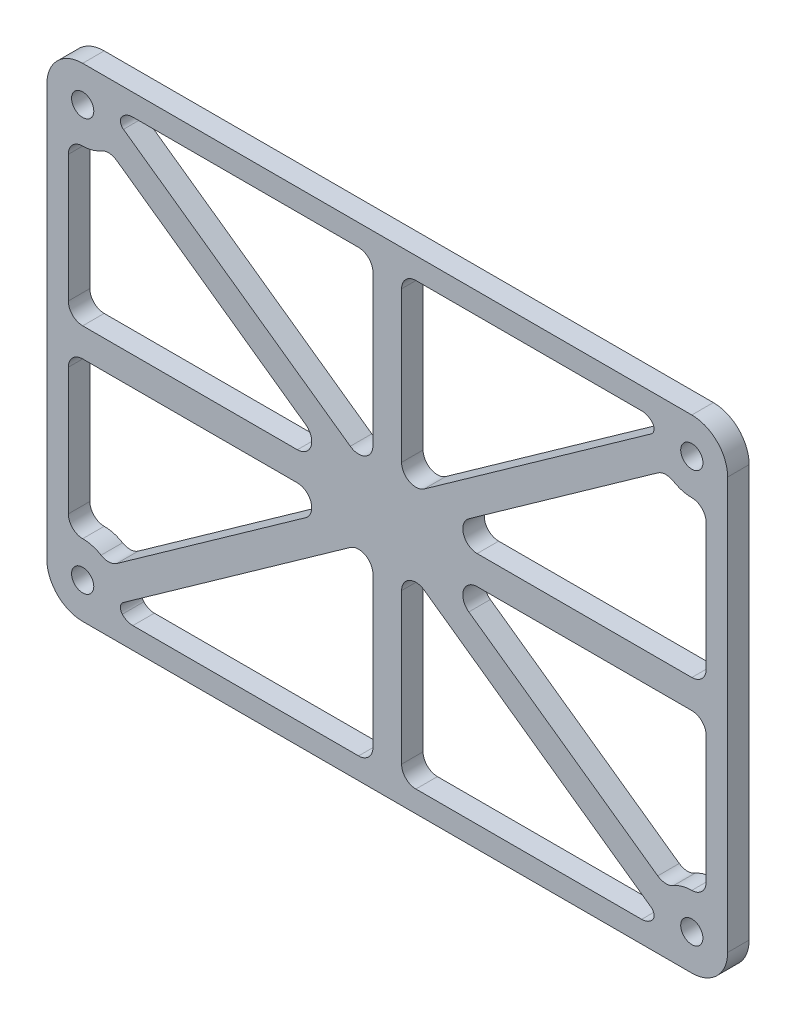
SolidWorks part; units mm, degrees
material "Thornel Mat VMA"
ref_plane "前视基准面" through (0, 0, 0) normal (0, 0, 1) x (1, 0, 0)
ref_plane "上视基准面" through (0, 0, 0) normal (0, 1, 0) x (1, 0, 0)
ref_plane "右视基准面" through (0, 0, 0) normal (1, 0, 0) x (0, 0, -1)
sketch "草图1" plane through (0, 0, 0) normal (0, 0, 1) x (1, 0, 0)
  line L0 (0, 0) -> (-50000, 0) construction
  line L1 (47.5, -33.725) -> (-47.5, -33.725)
  line L2 (47.5, -33.725) -> (47.5, 33.725)
  line L3 (47.5, 33.725) -> (-47.5, 33.725)
  line L4 (-47.5, -33.725) -> (-47.5, 33.725)
  line L5 (47.5, -33.725) -> (-47.5, 33.725) construction
  line L6 (47.5, 33.725) -> (-47.5, -33.725) construction
  line L7 (0, 0) -> (0, 50000) construction
  line L8 (-44.5, -2) -> (-44.5, -24.1424)
  line L9 (-6.2716, -2) -> (-38.9514, -25.2026)
  line L10 (-44.5, -2) -> (-6.2716, -2)
  line L11 (-6.2716, 2) -> (-38.9514, 25.2026)
  line L12 (-44.5, 2) -> (-6.2716, 2)
  line L13 (-44.5, 2) -> (-44.5, 24.1424)
  line L14 (-2, 30.725) -> (-37.9174, 30.725)
  line L15 (-2, 3.8728) -> (-37.5131, 29.0872)
  line L16 (-2, 3.8728) -> (-2, 30.725)
  line L17 (-2, -3.8728) -> (-2, -30.725)
  line L18 (-2, -30.725) -> (-37.9174, -30.725)
  line L19 (-2, -3.8728) -> (-37.5131, -29.0872)
  line L20 (2, -30.725) -> (37.9174, -30.725)
  line L21 (2, -3.8728) -> (2, -30.725)
  line L22 (2, -3.8728) -> (37.5131, -29.0872)
  line L23 (6.2716, -2) -> (38.9514, -25.2026)
  line L24 (44.5, -2) -> (6.2716, -2)
  line L25 (44.5, -2) -> (44.5, -24.1424)
  line L26 (44.5, 2) -> (6.2716, 2)
  line L27 (6.2716, 2) -> (38.9514, 25.2026)
  line L28 (44.5, 2) -> (44.5, 24.1424)
  line L29 (2, 3.8728) -> (2, 30.725)
  line L30 (2, 3.8728) -> (37.5131, 29.0872)
  line L31 (2, 30.725) -> (37.9174, 30.725)
  circle A0 centre (-42.5, 28.725) radius 1.55
  circle A2 centre (42.5, 28.725) radius 1.55
  circle A3 centre (42.5, -28.725) radius 1.55
  circle A4 centre (-42.5, -28.725) radius 1.55
  circle A5 centre (-42.5, 28.725) radius 5
  circle A6 centre (-42.5, -28.725) radius 5
  circle A7 centre (42.5, -28.725) radius 5
  circle A8 centre (42.5, 28.725) radius 5
  point P0 (0, 0)
  dimension "D1" = 3.1
  dimension "D5" = 5
  dimension "D6" = 10
  dimension "D2" = 85
  dimension "D3" = 57.45
  dimension "D4" = 5
  dimension "D7" = 2
  dimension "D8" = 3
  dimension "D9" = 4
  dimension "D10" = 3
  dimension "D11" = 2
extrude "凸台-拉伸1" add sketch "草图1" along normal blind 3 contours A8 L3 A5 L14 L16 L15 L11 L12 L13 L4 A6 L8 L10 L9 L19 L17 L18 L1 A7 L20 L21 L22 L23 L24 L25 L2 L28 L26 L27 L30 L29 L31 | A5 A0 | A8 A2 | A7 A3 | A6 A4 region at (0, 0, 0) region at (39.8388, -32.79, 0) region at (-45.9355, -32.1605, 0) region at (46.565, 26.0638, 0) region at (-45.9355, 32.1605, 0)
fillet "圆角1" radius 2 32 edges at (38.9514, 25.2026, 1.5) (6.2716, 2, 1.5) (44.5, 2, 1.5) (44.5, 24.1424, 1.5) (44.5, -24.1424, 1.5) (44.5, -2, 1.5) (6.2716, -2, 1.5) (38.9514, -25.2026, 1.5) (2, -3.8728, 1.5) (2, -30.725, 1.5) (37.9174, -30.725, 1.5) (37.5131, -29.0872, 1.5) (-37.9174, -30.725, 1.5) (-2, -30.725, 1.5) (-2, -3.8728, 1.5) (-37.5131, -29.0872, 1.5) (-6.2716, -2, 1.5) (-44.5, -2, 1.5) (-44.5, -24.1424, 1.5) (-38.9514, -25.2026, 1.5) (-44.5, 24.1424, 1.5) (-6.2716, 2, 1.5) (-38.9514, 25.2026, 1.5) (-2, 3.8728, 1.5) (-2, 30.725, 1.5) (-37.9174, 30.725, 1.5) (-37.5131, 29.0872, 1.5) (2, 30.725, 1.5) (2, 3.8728, 1.5) (37.5131, 29.0872, 1.5) (37.9174, 30.725, 1.5) (-44.5, 2, 1.5)
fillet "圆角2" radius 1 4 edges at (-37.4226, 29.2759, 1.5) (-37.4226, -29.2759, 1.5) (37.4226, -29.2759, 1.5) (37.4226, 29.2759, 1.5)
